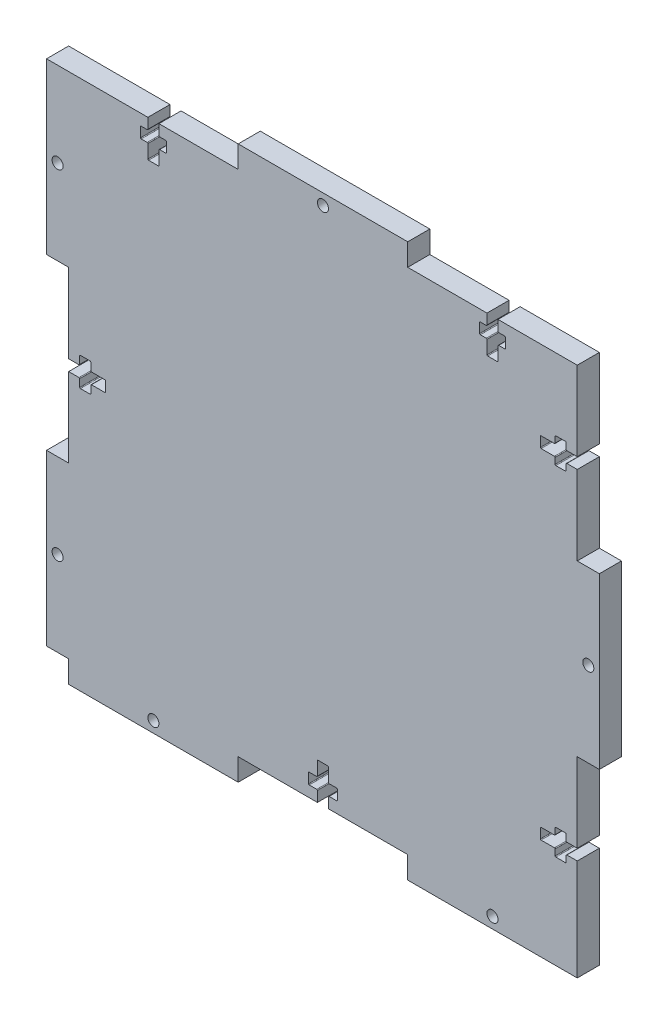
SolidWorks part; units mm, degrees
ref_plane "Front Plane" through (0, 0, 0) normal (0, 0, 1) x (1, 0, 0)
ref_plane "Top Plane" through (0, 0, 0) normal (0, 1, 0) x (1, 0, 0)
ref_plane "Right Plane" through (0, 0, 0) normal (1, 0, 0) x (0, 0, -1)
sketch "Sketch1" plane through (0, 0, 0) normal (0, 0, 1) x (1, 0, 0)
  line L0 (-69, 69) -> (-23, 69)
  line L5 (-75, -75) -> (75, -75) construction
  line L6 (-75, -75) -> (-75, 75) construction
  line L7 (-75, 75) -> (75, 75) construction
  line L8 (75, -75) -> (75, 75) construction
  line L9 (75, 23) -> (69, 23)
  line L10 (69, -23) -> (75, -23)
  line L11 (-69, -69) -> (69, -69) construction
  line L12 (-69, -69) -> (-69, 69) construction
  line L13 (-69, 69) -> (69, 69) construction
  line L14 (69, -69) -> (69, 69) construction
  line L15 (-69, -69) -> (69, 69) construction
  line L16 (69, -69) -> (69, -23)
  line L17 (-23, 69) -> (-23, 75)
  line L18 (-23, 75) -> (23, 75)
  line L19 (23, 75) -> (23, 69)
  line L20 (23, 69) -> (69, 69)
  line L21 (75, -23) -> (75, 23)
  line L22 (69, 23) -> (69, 69)
  line L23 (-75, 23) -> (-69, 23)
  line L24 (-69, 69) -> (-75, 69)
  line L25 (-75, 69) -> (-75, 23)
  line L26 (69, -69) -> (69, -75)
  line L27 (69, -75) -> (23, -75)
  line L28 (23, -75) -> (23, -69)
  line L29 (23, -69) -> (-23, -69)
  line L30 (-23, -69) -> (-23, -75)
  line L31 (-23, -75) -> (-69, -75)
  line L32 (-69, -75) -> (-69, -69)
  line L33 (-69, 23) -> (-69, -23)
  line L34 (-69, -23) -> (-75, -23)
  line L35 (-75, -23) -> (-75, -69)
  line L36 (-75, -69) -> (-69, -69)
  line L37 (-46, 69) -> (-46, -75) construction
  line L38 (-69, 69) -> (69, -69) construction
  point P0 (0, 0)
  point P6 (-7, -7)
  point P26 (0, -75)
  point P27 (-75, 0)
  dimension "D1" = 150
  dimension "D2" = 150
  dimension "D3" = 6
  dimension "D4" = 138
  dimension "D5" = 46
  dimension "D6" = 6
  dimension "D7" = 6
extrude "Box Side" add sketch "Sketch1" along normal blind 6
sketch "Sketch2" plane through (0, 0, 6) normal (0, 0, 1) x (1, 0, 0)
  line L0 (23, 72) -> (-23, 72) construction
  line L1 (23, 75) -> (23, 69) construction
  line L2 (-23, 69) -> (-23, 75) construction
  line L3 (-46, 69) -> (-46, -75) construction
  line L5 (0, 75) -> (0, 69) construction
  line L6 (-23, 75) -> (23, 75) construction
  line L7 (-69, 69) -> (69, 69) construction
  line L16 (-46, 69) -> (-46, -75) construction
  line L21 (0, -69) -> (0, 69) construction
  line L35 (-69, 69) -> (-23, 69) construction
  line L36 (-44.5, 69) -> (-44.5, 66.2)
  line L37 (-44.3, 66) -> (-42.7, 66)
  line L38 (-42.5, 65.8) -> (-42.5, 63.2)
  line L39 (-42.7, 63) -> (-44.3, 63)
  line L40 (-44.5, 62.8) -> (-44.5, 59.2)
  line L46 (-44.7, 59) -> (-47.3, 59)
  line L48 (-44.5, 69) -> (-47.5, 69)
  line L51 (-47.5, 62.8) -> (-47.5, 59.2)
  line L52 (-49.3, 63) -> (-47.7, 63)
  line L53 (-49.5, 65.8) -> (-49.5, 63.2)
  line L54 (-47.7, 66) -> (-49.3, 66)
  line L55 (-47.5, 69) -> (-47.5, 66.2)
  line L56 (47.5, 69) -> (47.5, 66.2)
  line L57 (47.7, 66) -> (49.3, 66)
  line L58 (49.5, 65.8) -> (49.5, 63.2)
  line L59 (49.3, 63) -> (47.7, 63)
  line L60 (47.5, 62.8) -> (47.5, 59.2)
  line L61 (44.5, 69) -> (47.5, 69)
  line L62 (44.7, 59) -> (47.3, 59)
  line L63 (44.5, 62.8) -> (44.5, 59.2)
  line L64 (42.7, 63) -> (44.3, 63)
  line L65 (42.5, 65.8) -> (42.5, 63.2)
  line L66 (44.3, 66) -> (42.7, 66)
  line L67 (44.5, 69) -> (44.5, 66.2)
  line L68 (-69, -69) -> (69, 69) construction
  line L69 (-69, -69) -> (69, 69) construction
  line L70 (75, 0) -> (69, 0) construction
  line L71 (72, 23) -> (72, -23) construction
  line L72 (69, 44.5) -> (66.2, 44.5)
  line L73 (66, 44.3) -> (66, 42.7)
  line L74 (65.8, 42.5) -> (63.2, 42.5)
  line L75 (63, 42.7) -> (63, 44.3)
  line L76 (62.8, 44.5) -> (59.2, 44.5)
  line L77 (59, 44.7) -> (59, 47.3)
  line L78 (69, 44.5) -> (69, 47.5)
  line L79 (62.8, 47.5) -> (59.2, 47.5)
  line L80 (63, 49.3) -> (63, 47.7)
  line L81 (65.8, 49.5) -> (63.2, 49.5)
  line L82 (66, 47.7) -> (66, 49.3)
  line L83 (69, 47.5) -> (66.2, 47.5)
  line L84 (69, -47.5) -> (66.2, -47.5)
  line L85 (66, -47.7) -> (66, -49.3)
  line L86 (65.8, -49.5) -> (63.2, -49.5)
  line L87 (63, -49.3) -> (63, -47.7)
  line L88 (62.8, -47.5) -> (59.2, -47.5)
  line L89 (69, -44.5) -> (69, -47.5)
  line L90 (59, -44.7) -> (59, -47.3)
  line L91 (62.8, -44.5) -> (59.2, -44.5)
  line L92 (63, -42.7) -> (63, -44.3)
  line L93 (65.8, -42.5) -> (63.2, -42.5)
  line L94 (66, -44.3) -> (66, -42.7)
  line L95 (69, -44.5) -> (66.2, -44.5)
  line L120 (-69, 69) -> (69, -69) construction
  line L121 (-69, 69) -> (69, -69) construction
  line L122 (-1.5, -69) -> (1.5, -69)
  line L123 (-23, -69) -> (23, -69) construction
  line L124 (1.5, -69) -> (1.5, -66.2)
  line L125 (1.7, -66) -> (3.7, -66)
  line L126 (3.9, -65.8) -> (3.9, -63.2)
  line L127 (3.7, -63) -> (1.7, -63)
  line L128 (1.5, -62.8) -> (1.5, -59.2)
  line L129 (1.3, -59) -> (-1.3, -59)
  line L130 (-1.5, -62.8) -> (-1.5, -59.2)
  line L131 (-3.7, -63) -> (-1.7, -63)
  line L132 (-3.9, -65.8) -> (-3.9, -63.2)
  line L133 (-1.7, -66) -> (-3.7, -66)
  line L134 (-1.5, -69) -> (-1.5, -66.2)
  line L135 (-69, -1.5) -> (-66.2, -1.5)
  line L136 (-66, -1.7) -> (-66, -3.7)
  line L137 (-65.8, -3.9) -> (-63.2, -3.9)
  line L138 (-63, -3.7) -> (-63, -1.7)
  line L139 (-62.8, -1.5) -> (-59.2, -1.5)
  line L140 (-59, 1.3) -> (-59, -1.3)
  line L141 (-62.8, 1.5) -> (-59.2, 1.5)
  line L142 (-63, 3.7) -> (-63, 1.7)
  line L143 (-65.8, 3.9) -> (-63.2, 3.9)
  line L144 (-66, 1.7) -> (-66, 3.7)
  line L145 (-69, 1.5) -> (-66.2, 1.5)
  line L146 (-69, -1.5) -> (-69, 1.5)
  line L147 (-69, -72) -> (-23, -72) construction
  line L148 (-69, -69) -> (-69, -75) construction
  line L149 (-23, -75) -> (-23, -69) construction
  circle A0 centre (0, 72) radius 1.5
  arc A1 (-44.5, 59.2) -> (-44.7, 59) centre (-44.7, 59.2) cw
  arc A2 (-44.3, 63) -> (-44.5, 62.8) centre (-44.3, 62.8) ccw
  arc A3 (-42.5, 63.2) -> (-42.7, 63) centre (-42.7, 63.2) cw
  arc A4 (-42.7, 66) -> (-42.5, 65.8) centre (-42.7, 65.8) cw
  arc A5 (-44.5, 66.2) -> (-44.3, 66) centre (-44.3, 66.2) ccw
  arc A6 (-47.5, 66.2) -> (-47.7, 66) centre (-47.7, 66.2) cw
  arc A7 (-49.3, 66) -> (-49.5, 65.8) centre (-49.3, 65.8) ccw
  arc A8 (-49.5, 63.2) -> (-49.3, 63) centre (-49.3, 63.2) ccw
  arc A9 (-47.7, 63) -> (-47.5, 62.8) centre (-47.7, 62.8) cw
  arc A10 (-47.5, 59.2) -> (-47.3, 59) centre (-47.3, 59.2) ccw
  arc A11 (47.5, 59.2) -> (47.3, 59) centre (47.3, 59.2) cw
  arc A12 (47.7, 63) -> (47.5, 62.8) centre (47.7, 62.8) ccw
  arc A13 (49.5, 63.2) -> (49.3, 63) centre (49.3, 63.2) cw
  arc A14 (49.3, 66) -> (49.5, 65.8) centre (49.3, 65.8) cw
  arc A15 (47.5, 66.2) -> (47.7, 66) centre (47.7, 66.2) ccw
  arc A16 (44.5, 66.2) -> (44.3, 66) centre (44.3, 66.2) cw
  arc A17 (42.7, 66) -> (42.5, 65.8) centre (42.7, 65.8) ccw
  arc A18 (42.5, 63.2) -> (42.7, 63) centre (42.7, 63.2) ccw
  arc A19 (44.3, 63) -> (44.5, 62.8) centre (44.3, 62.8) cw
  arc A20 (44.5, 59.2) -> (44.7, 59) centre (44.7, 59.2) ccw
  arc A21 (59.2, 44.5) -> (59, 44.7) centre (59.2, 44.7) cw
  arc A22 (63, 44.3) -> (62.8, 44.5) centre (62.8, 44.3) ccw
  arc A23 (63.2, 42.5) -> (63, 42.7) centre (63.2, 42.7) cw
  arc A24 (66, 42.7) -> (65.8, 42.5) centre (65.8, 42.7) cw
  arc A25 (66.2, 44.5) -> (66, 44.3) centre (66.2, 44.3) ccw
  arc A26 (66.2, 47.5) -> (66, 47.7) centre (66.2, 47.7) cw
  arc A27 (66, 49.3) -> (65.8, 49.5) centre (65.8, 49.3) ccw
  arc A28 (63.2, 49.5) -> (63, 49.3) centre (63.2, 49.3) ccw
  arc A29 (63, 47.7) -> (62.8, 47.5) centre (62.8, 47.7) cw
  arc A30 (59.2, 47.5) -> (59, 47.3) centre (59.2, 47.3) ccw
  arc A31 (59.2, -47.5) -> (59, -47.3) centre (59.2, -47.3) cw
  arc A32 (63, -47.7) -> (62.8, -47.5) centre (62.8, -47.7) ccw
  arc A33 (63.2, -49.5) -> (63, -49.3) centre (63.2, -49.3) cw
  arc A34 (66, -49.3) -> (65.8, -49.5) centre (65.8, -49.3) cw
  arc A35 (66.2, -47.5) -> (66, -47.7) centre (66.2, -47.7) ccw
  arc A36 (66.2, -44.5) -> (66, -44.3) centre (66.2, -44.3) cw
  arc A37 (66, -42.7) -> (65.8, -42.5) centre (65.8, -42.7) ccw
  arc A38 (63.2, -42.5) -> (63, -42.7) centre (63.2, -42.7) ccw
  arc A39 (63, -44.3) -> (62.8, -44.5) centre (62.8, -44.3) cw
  arc A40 (59.2, -44.5) -> (59, -44.7) centre (59.2, -44.7) ccw
  circle A41 centre (72, 0) radius 1.5
  arc A62 (1.5, -59.2) -> (1.3, -59) centre (1.3, -59.2) ccw
  arc A63 (1.7, -63) -> (1.5, -62.8) centre (1.7, -62.8) cw
  arc A64 (3.9, -63.2) -> (3.7, -63) centre (3.7, -63.2) ccw
  arc A65 (3.7, -66) -> (3.9, -65.8) centre (3.7, -65.8) ccw
  arc A66 (1.5, -66.2) -> (1.7, -66) centre (1.7, -66.2) cw
  arc A67 (-1.5, -66.2) -> (-1.7, -66) centre (-1.7, -66.2) ccw
  arc A68 (-3.7, -66) -> (-3.9, -65.8) centre (-3.7, -65.8) cw
  arc A69 (-3.9, -63.2) -> (-3.7, -63) centre (-3.7, -63.2) cw
  arc A70 (-1.7, -63) -> (-1.5, -62.8) centre (-1.7, -62.8) ccw
  arc A71 (-1.5, -59.2) -> (-1.3, -59) centre (-1.3, -59.2) cw
  arc A72 (-59.2, -1.5) -> (-59, -1.3) centre (-59.2, -1.3) ccw
  arc A73 (-63, -1.7) -> (-62.8, -1.5) centre (-62.8, -1.7) cw
  arc A74 (-63.2, -3.9) -> (-63, -3.7) centre (-63.2, -3.7) ccw
  arc A75 (-66, -3.7) -> (-65.8, -3.9) centre (-65.8, -3.7) ccw
  arc A76 (-66.2, -1.5) -> (-66, -1.7) centre (-66.2, -1.7) cw
  arc A77 (-66.2, 1.5) -> (-66, 1.7) centre (-66.2, 1.7) ccw
  arc A78 (-66, 3.7) -> (-65.8, 3.9) centre (-65.8, 3.7) cw
  arc A79 (-63.2, 3.9) -> (-63, 3.7) centre (-63.2, 3.7) cw
  arc A80 (-63, 1.7) -> (-62.8, 1.5) centre (-62.8, 1.7) ccw
  arc A81 (-59.2, 1.5) -> (-59, 1.3) centre (-59.2, 1.3) cw
  circle A82 centre (-46, -72) radius 1.5
  circle A83 centre (46, -72) radius 1.5
  circle A84 centre (-72, 46) radius 1.5
  circle A85 centre (-72, -46) radius 1.5
  point P6 (0, 72)
  point P38 (0, 0)
  point P56 (-46, 59)
  point P88 (46, 59)
  point P161 (59, 46)
  point P162 (59, -46)
  point P198 (0, -59)
  point P231 (-59, 0)
  dimension "D1" = 3
  dimension "D2" = 0.2
  dimension "D8" = 0.2
  dimension "D14" = 3
  dimension "D3" = 3
  dimension "D4" = 3
  dimension "D5" = 4
  dimension "D6" = 2
  dimension "D7" = 1.5
  dimension "D9" = 3
  dimension "D10" = 3
  dimension "D11" = 4
  dimension "D12" = 1.5
  dimension "D13" = 2
extrude "Screw Cut-outs" cut sketch "Sketch2" against normal through all
